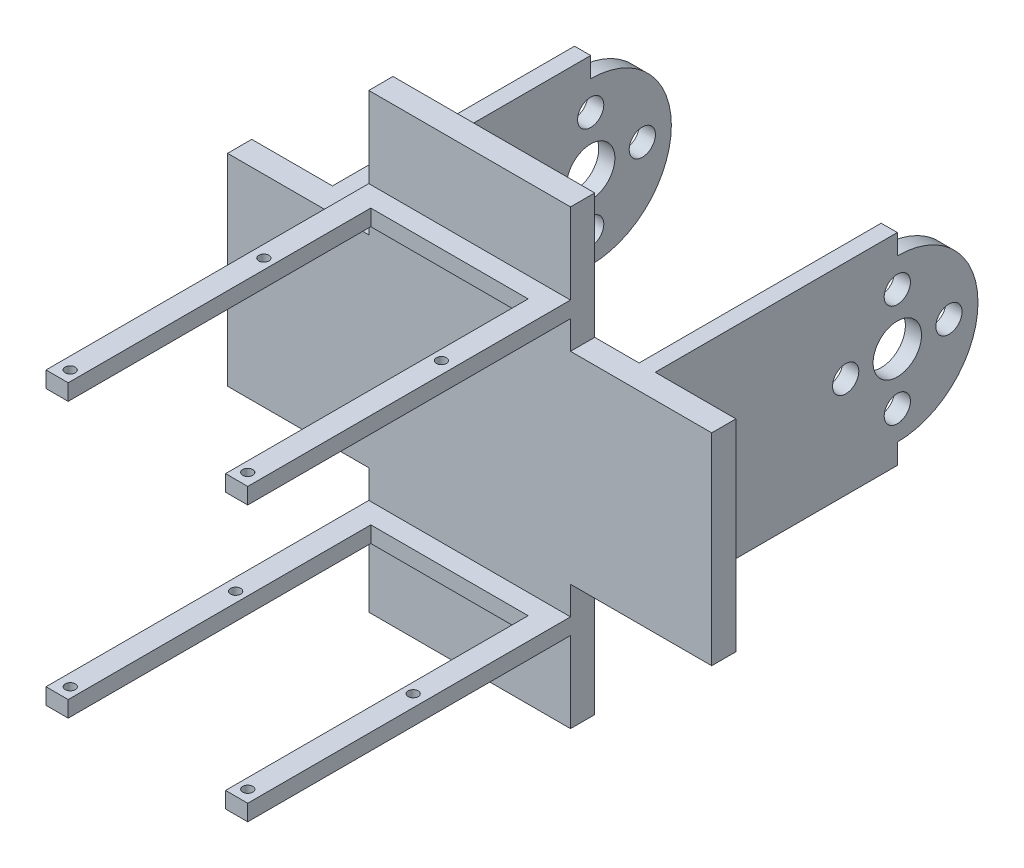
SolidWorks part; units mm, degrees
ref_plane "Front Plane" through (0, 0, 0) normal (0, 0, 1) x (1, 0, 0)
ref_plane "Top Plane" through (0, 0, 0) normal (0, 1, 0) x (1, 0, 0)
ref_plane "Right Plane" through (0, 0, 0) normal (1, 0, 0) x (0, 0, -1)
sketch "Sketch1" plane through (0, 0, 0) normal (0, 0, 1) x (1, 0, 0)
  line L0 (12.5, 12.5) -> (20, 12.5)
  line L1 (-12.5, 18) -> (12.5, 18)
  line L2 (-12.5, 18) -> (-12.5, 12.5)
  line L3 (-12.5, -18) -> (12.5, -18)
  line L4 (12.5, 18) -> (12.5, 12.5)
  line L5 (-12.5, 18) -> (12.5, -18) construction
  line L6 (-12.5, -18) -> (12.5, 18) construction
  line L7 (-20, 12.5) -> (-12.5, 12.5)
  line L8 (-20, 12.5) -> (-20, -12.5)
  line L9 (-20, -12.5) -> (-12.5, -12.5)
  line L10 (20, 12.5) -> (20, -12.5)
  line L11 (-20, 12.5) -> (20, -12.5) construction
  line L12 (-20, -12.5) -> (20, 12.5) construction
  line L13 (-12.5, -12.5) -> (-12.5, -18)
  line L14 (12.5, -12.5) -> (20, -12.5)
  line L15 (12.5, -12.5) -> (12.5, -18)
  point P0 (0, 0)
  point P6 (0, 0)
  dimension "D1" = 25
  dimension "D2" = 36
  dimension "D3" = 25
  dimension "D4" = 40
extrude "Boss-Extrude1" add sketch "Sketch1" along normal blind 3
sketch "Sketch2" plane through (0, 0, 3) normal (0, 0, 1) x (1, 0, 0)
  line L0 (12.5, 12.5) -> (12.5, 18) construction
  line L1 (-12.5, 18) -> (12.5, 18)
  line L2 (-12.5, 18) -> (-12.5, 16)
  line L3 (-12.5, 16) -> (12.5, 16)
  line L4 (12.5, 18) -> (12.5, 16)
  line L5 (-12.5, 18) -> (12.5, 16) construction
  line L6 (-12.5, 16) -> (12.5, 18) construction
  line L7 (12.5, -18) -> (12.5, -12.5) construction
  line L8 (-12.5, -16) -> (12.5, -16)
  line L9 (-12.5, -16) -> (-12.5, -18)
  line L10 (-12.5, -18) -> (12.5, -18)
  line L11 (12.5, -16) -> (12.5, -18)
  line L12 (-12.5, -16) -> (12.5, -18) construction
  line L13 (-12.5, -18) -> (12.5, -16) construction
  line L14 (12.5, 18) -> (-12.5, 18) construction
  point P0 (0, 17)
  point P7 (0, -17)
  dimension "D1" = 2
  dimension "D2" = 2
  dimension "D3" = 0
  dimension "D4" = 0
extrude "Boss-Extrude2" add sketch "Sketch2" along normal blind 40
sketch "Sketch3" plane through (0, 18, 0) normal (0, 1, 0) x (1, 0, 0)
  line L0 (-12.5, -43) -> (-12.5, 0) construction
  line L1 (12.5, -43) -> (12.5, 0) construction
  line L2 (12.5, -43) -> (-12.5, -43) construction
  circle A0 centre (-11, -17.5) radius 0.625
  circle A1 centre (11, -17.5) radius 0.625
  circle A2 centre (-11, -41.5) radius 0.625
  circle A3 centre (11, -41.5) radius 0.625
  dimension "D3" = 1.25
  dimension "D4" = 1.25
  dimension "D6" = 1.25
  dimension "D7" = 1.25
  dimension "D1" = 1.5
  dimension "D2" = 1.5
  dimension "D5" = 24
  dimension "D8" = 1.5
  dimension "D9" = 1.5
  dimension "D10" = 1.5
  dimension "D11" = 1.5
extrude "Cut-Extrude1" cut sketch "Sketch3" against normal blind 3
sketch "Sketch4" plane through (0, -16, 0) normal (0, 1, 0) x (1, 0, 0)
  circle A0 centre (-11, -41.5) radius 0.625
  circle A1 centre (11, -41.5) radius 0.625
  circle A2 centre (-11, -21) radius 0.625
  circle A3 centre (11, -21) radius 0.625
  point P10 (0, 0)
  dimension "D1" = 1.25
  dimension "D2" = 1.25
  dimension "D3" = 20.5
extrude "Cut-Extrude2" cut sketch "Sketch4" against normal blind 3
sketch "Sketch5" plane through (0, 0, 0) normal (0, 0, -1) x (-1, 0, 0)
  line L0 (-12.5, -12.5) -> (-20, -12.5) construction
  line L1 (-20, 12.5) -> (-18, 12.5)
  line L2 (-20, 12.5) -> (-20, -12.5)
  line L3 (-20, -12.5) -> (-18, -12.5)
  line L4 (-18, 12.5) -> (-18, -12.5)
  line L5 (-20, 12.5) -> (-18, -12.5) construction
  line L6 (-20, -12.5) -> (-18, 12.5) construction
  line L7 (12.5, 12.5) -> (20, 12.5) construction
  line L8 (20, -12.5) -> (18, -12.5)
  line L9 (20, -12.5) -> (20, 12.5)
  line L10 (20, 12.5) -> (18, 12.5)
  line L11 (18, -12.5) -> (18, 12.5)
  line L12 (20, -12.5) -> (18, 12.5) construction
  line L13 (20, 12.5) -> (18, -12.5) construction
  point P0 (-19, 0)
  point P7 (19, 0)
  dimension "D1" = 2
  dimension "D2" = 2
  dimension "D3" = 5.5
  dimension "D4" = 0
extrude "Boss-Extrude3" add sketch "Sketch5" along normal blind 40
sketch "Sketch6" plane through (20, 0, 0) normal (1, 0, 0) x (0, 0, -1)
  line L0 (30, 10) -> (30, 12.5)
  line L1 (-3, 12.5) -> (40, 12.5) construction
  line L2 (30, 12.5) -> (46.4573, 12.5)
  line L3 (46.4573, 12.5) -> (46.4573, -12.5)
  line L4 (46.4573, -12.5) -> (30, -12.5)
  line L5 (-3, -12.5) -> (40, -12.5) construction
  line L6 (30, -12.5) -> (30, -10)
  arc A0 (30, -10) -> (30, 10) centre (30, 0) ccw
  circle A1 centre (30, 6.3983) radius 1.625
  circle A2 centre (30, 0) radius 3
  circle A3 centre (36.3983, 0) radius 1.625
  circle A4 centre (30, -6.3983) radius 1.625
  circle A5 centre (23.6017, 0) radius 1.625
  dimension "D1" = 20
  dimension "D2" = 30
  dimension "D3" = 4
extrude "Cut-Extrude4" cut sketch "Sketch6" against normal blind 40
sketch "Sketch7" plane through (0, 18, 0) normal (0, 1, 0) x (1, 0, 0)
  line L0 (12.5, -43) -> (-12.5, -43) construction
  line L1 (-9.75, -80.5) -> (9.75, -80.5)
  line L2 (-9.75, -80.5) -> (-9.75, -5.5)
  line L3 (-9.75, -5.5) -> (9.75, -5.5)
  line L4 (9.75, -80.5) -> (9.75, -5.5)
  line L5 (-9.75, -80.5) -> (9.75, -5.5) construction
  line L6 (-9.75, -5.5) -> (9.75, -80.5) construction
  point P0 (0, -43)
  dimension "D1" = 75
  dimension "D2" = 19.5
extrude "Cut-Extrude5" cut sketch "Sketch7" against normal blind 40
sketch "Sketch10" plane through (0, 18, 0) normal (0, 1, 0) x (1, 0, 0)
  line L1 (-12.5, 0) -> (12.5, 0)
  line L2 (-12.5, 0) -> (-12.5, -3)
  line L3 (-12.5, -3) -> (12.5, -3)
  line L4 (12.5, 0) -> (12.5, -3)
extrude "Boss-Extrude4" add sketch "Sketch10" along normal blind 10
sketch "Sketch11" plane through (0, -18, 0) normal (0, -1, 0) x (1, 0, 0)
  line L0 (12.5, 43) -> (12.5, 0) construction
  line L1 (-12.5, 0) -> (12.5, 0)
  line L2 (-12.5, 0) -> (-12.5, 3)
  line L3 (-12.5, 3) -> (12.5, 3)
  line L4 (12.5, 0) -> (12.5, 3)
extrude "Boss-Extrude5" add sketch "Sketch11" along normal blind 10
sketch "Sketch12" plane through (-20, 0, 0) normal (-1, 0, 0) x (0, 0, 1)
  line L0 (3, -12.5) -> (-30, -12.5) construction
  line L1 (3, 12.5) -> (0, 12.5)
  line L2 (3, 12.5) -> (3, -12.5)
  line L3 (3, -12.5) -> (0, -12.5)
  line L4 (0, 12.5) -> (0, -12.5)
  line L5 (0, -12.5) -> (0, -28) construction
extrude "Boss-Extrude6" add sketch "Sketch12" along normal blind 10
sketch "Sketch13" plane through (20, 0, 0) normal (1, 0, 0) x (0, 0, -1)
  line L0 (-3, -12.5) -> (30, -12.5) construction
  line L1 (-3, 12.5) -> (0, 12.5)
  line L2 (-3, 12.5) -> (-3, -12.5)
  line L3 (-3, -12.5) -> (0, -12.5)
  line L4 (0, 12.5) -> (0, -12.5)
extrude "Boss-Extrude7" add sketch "Sketch13" along normal blind 10
